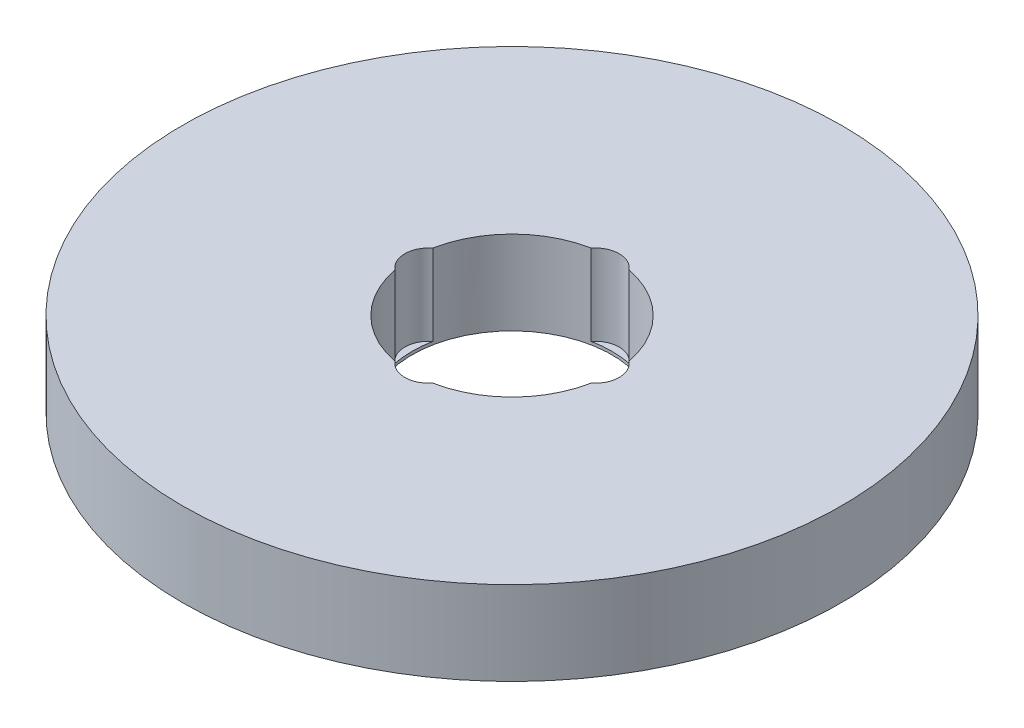
SolidWorks part; units mm, degrees
ref_plane "Front Plane" through (0, 0, 0) normal (0, 0, 1) x (1, 0, 0)
ref_plane "Top Plane" through (0, 0, 0) normal (0, 1, 0) x (1, 0, 0)
ref_plane "Right Plane" through (0, 0, 0) normal (1, 0, 0) x (0, 0, -1)
sketch "Sketch1" plane through (0, 0, 0) normal (0, 1, 0) x (1, 0, 0)
  circle A0 centre (0, 0) radius 82.5
  dimension "FLANGE_OD" = 165
extrude "Boss-Extrude1" add sketch "Sketch1" along normal blind 21
sketch "Sketch2" plane through (0, 0, 0) normal (0, 1, 0) x (1, 0, 0)
  circle A0 centre (0, 0) radius 25
  dimension "BORE_D" = 50
extrude "Cut-Extrude1" cut sketch "Sketch2" along normal through all
sketch "Sketch3" plane through (0, 21, 0) normal (0, 1, 0) x (1, 0, 0)
  circle A0 centre (0, 0) radius 20.8051 construction
  circle A1 centre (-20.8051, 0) radius 6.0248
  dimension "BOLT_D" = 12.0496
  dimension "BOLT_PCD" = 41.6101
extrude "Cut-Extrude2" cut sketch "Sketch3" against normal blind 20.2365
pattern_circular "CirPattern1" count 4 over 360 about axis through (0, 0, 0) along (0, 1, 0) of "Cut-Extrude2"
